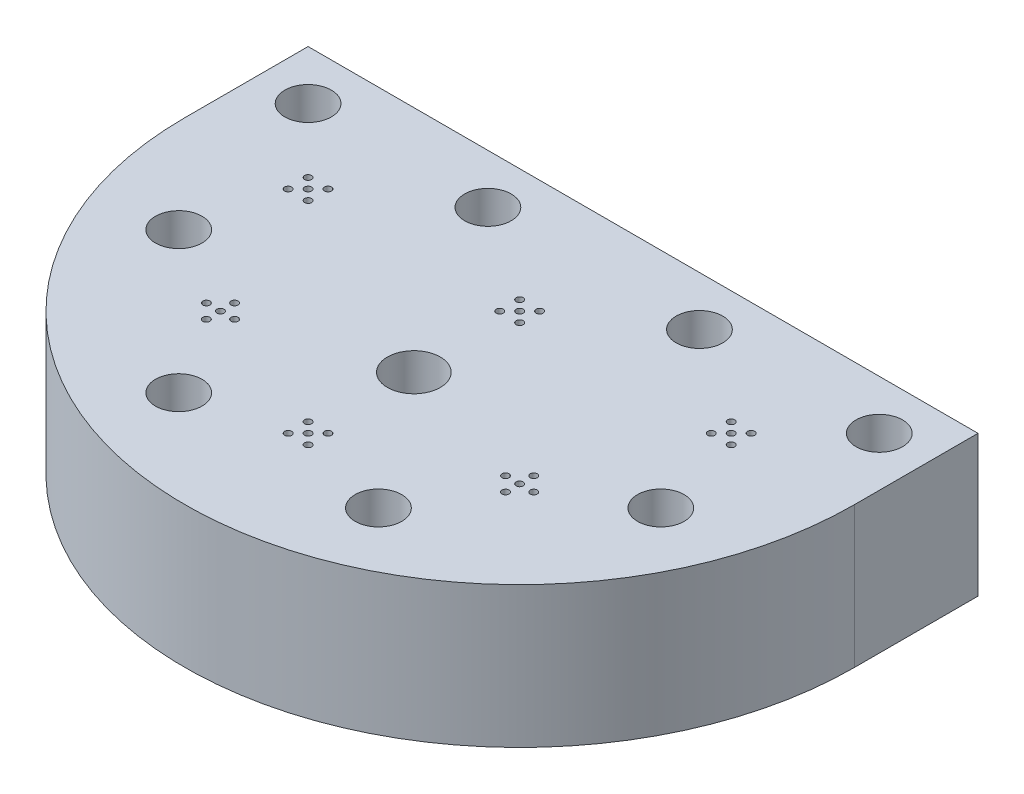
SolidWorks part; units mm, degrees
ref_plane "Front Plane" through (0, 0, 0) normal (0, 0, 1) x (1, 0, 0)
ref_plane "Top Plane" through (0, 0, 0) normal (0, 1, 0) x (1, 0, 0)
ref_plane "Right Plane" through (0, 0, 0) normal (1, 0, 0) x (0, 0, -1)
sketch "Sketch1" plane through (0, 0, 0) normal (0, 1, 0) x (1, 0, 0)
  line L0 (-47.5, 0) -> (47.5, 0)
  line L1 (-47.5, 0) -> (-47.5, -17.5)
  line L2 (47.5, 0) -> (47.5, -17.5)
  arc A0 (-47.5, -17.5) -> (47.5, -17.5) centre (0, -17.5) ccw
  point P4 (0, 0)
  dimension "D1" = 95
  dimension "D2" = 17.5
extrude "Boss-Extrude1" add sketch "Sketch1" along normal blind 20
sketch "Sketch2" plane through (0, 0, 0) normal (0, -1, 0) x (1, 0, 0)
  line L0 (30, 17.5) -> (-30, 17.5) construction
  line L1 (47.5, 0) -> (-47.5, 0) construction
  line L2 (0, 17.5) -> (21.2132, 38.7132) construction
  line L3 (0, 17.5) -> (-21.2132, 38.7132) construction
  arc A0 (30, 17.5) -> (-30, 17.5) centre (0, 17.5) ccw construction
  circle A1 centre (30, 17.5) radius 7.5
  circle A2 centre (0, 17.5) radius 7.5
  circle A3 centre (-30, 17.5) radius 7.5
  circle A4 centre (0, 47.5) radius 7.5
  circle A5 centre (-21.2132, 38.7132) radius 7.5
  circle A6 centre (21.2132, 38.7132) radius 7.5
  dimension "D1" = 60
  dimension "D3" = 15
  dimension "D2" = 17.5
  dimension "D4" = 45
  dimension "D5" = 45
extrude "Cut-Extrude1" cut sketch "Sketch2" against normal blind 9.5
ref_plane "Plane1" through (0, 0, 17.5) normal (0, 0, -1) x (-1, 0, 0)
sketch "Sketch3" plane through (0, 0, 17.5) normal (0, 0, -1) x (-1, 0, 0)
  line L0 (0, 9.5) -> (0, 17)
  line L1 (0, 9.5) -> (7.5, 9.5)
  line L2 (-7.5, 9.5) -> (7.5, 9.5) construction
  arc A0 (0, 17) -> (7.5, 9.5) centre (0, 9.5) cw
  point P4 (17.951, 11.8486)
  point P6 (0, 0)
  point P8 (0, 0)
  dimension "D1" = 7.5
revolve "Cut-Revolve1" cut sketch "Sketch3" angle 360 about L0
sketch "Sketch4" plane through (0, 0, 17.5) normal (0, 0, -1) x (-1, 0, 0)
  line L0 (-30, 9.5) -> (-30, 17)
  line L1 (-30, 9.5) -> (-22.5, 9.5)
  line L2 (-37.5, 9.5) -> (-22.5, 9.5) construction
  line L3 (-37.5, 9.5) -> (-22.5, 9.5) construction
  arc A0 (-30, 17) -> (-22.5, 9.5) centre (-30, 9.5) cw
  point P4 (0, 0)
  point P6 (0, 0)
  point P7 (-30.2611, 9.5)
  point P8 (-30, 9.5)
  point P9 (0, 0)
revolve "Cut-Revolve2" cut sketch "Sketch4" angle 360 about L0
ref_axis "Axis1" through (0, 9.5, 17.5) along (0, -1, 0)
pattern_circular "CirPattern1" count 5 every 45 about axis through (0, 9.5, 17.5) along (0, -1, 0) of "Cut-Revolve2"
sketch "Sketch5" plane through (0, 20, 0) normal (0, 1, 0) x (1, 0, 0)
  line L1 (1.4142, -18.9142) -> (-1.4142, -18.9142) construction
  line L2 (1.4142, -18.9142) -> (1.4142, -16.0858) construction
  line L3 (1.4142, -16.0858) -> (-1.4142, -16.0858) construction
  line L4 (-1.4142, -18.9142) -> (-1.4142, -16.0858) construction
  line L5 (1.4142, -18.9142) -> (-1.4142, -16.0858) construction
  line L6 (1.4142, -16.0858) -> (-1.4142, -18.9142) construction
  circle A0 centre (30, -17.5) radius 7.5 construction
  circle A1 centre (21.2132, -38.7132) radius 7.5 construction
  circle A2 centre (0, -17.5) radius 7.5 construction
  circle A3 centre (-30, -17.5) radius 7.5 construction
  circle A4 centre (-21.2132, -38.7132) radius 7.5 construction
  circle A5 centre (0, -47.5) radius 7.5 construction
  circle A6 centre (30, -17.5) radius 7.5 construction
  circle A7 centre (21.2132, -38.7132) radius 7.5 construction
  circle A8 centre (0, -17.5) radius 7.5 construction
  circle A9 centre (-30, -17.5) radius 7.5 construction
  circle A10 centre (-21.2132, -38.7132) radius 7.5 construction
  circle A11 centre (0, -47.5) radius 7.5 construction
  circle A12 centre (21.2132, -38.7132) radius 0.5
  circle A13 centre (21.2132, -38.7132) radius 2 construction
  circle A14 centre (21.2132, -40.7132) radius 0.5
  circle A15 centre (19.2132, -38.7132) radius 0.5
  circle A16 centre (23.2132, -38.7132) radius 0.5
  circle A17 centre (21.2132, -36.7132) radius 0.5
  circle A18 centre (1.4142, -46.0858) radius 0.5
  circle A19 centre (0, -47.5) radius 2 construction
  circle A20 centre (1.4142, -48.9142) radius 0.5
  circle A21 centre (0, -47.5) radius 0.5
  circle A22 centre (-1.4142, -46.0858) radius 0.5
  circle A23 centre (-1.4142, -48.9142) radius 0.5
  circle A24 centre (-19.2132, -38.7132) radius 0.5
  circle A25 centre (-21.2132, -38.7132) radius 2 construction
  circle A26 centre (-21.2132, -40.7132) radius 0.5
  circle A27 centre (-21.2132, -38.7132) radius 0.5
  circle A28 centre (-21.2132, -36.7132) radius 0.5
  circle A29 centre (-23.2132, -38.7132) radius 0.5
  circle A30 centre (-28.5858, -18.9142) radius 0.5
  circle A31 centre (-30, -17.5) radius 2 construction
  circle A32 centre (-31.4142, -18.9142) radius 0.5
  circle A33 centre (-30, -17.5) radius 0.5
  circle A34 centre (-28.5858, -16.0858) radius 0.5
  circle A35 centre (-31.4142, -16.0858) radius 0.5
  circle A36 centre (-21.2132, 1.7132) radius 0.5 [skipped]
  circle A37 centre (-21.2132, 3.7132) radius 2 construction
  circle A38 centre (-23.2132, 3.7132) radius 0.5 [skipped]
  circle A39 centre (-21.2132, 3.7132) radius 0.5 [skipped]
  circle A40 centre (-19.2132, 3.7132) radius 0.5 [skipped]
  circle A41 centre (-21.2132, 5.7132) radius 0.5 [skipped]
  circle A42 centre (-1.4142, 11.0858) radius 0.5 [skipped]
  circle A43 centre (0, 12.5) radius 2 construction
  circle A44 centre (-1.4142, 13.9142) radius 0.5 [skipped]
  circle A45 centre (0, 12.5) radius 0.5 [skipped]
  circle A46 centre (1.4142, 11.0858) radius 0.5 [skipped]
  circle A47 centre (1.4142, 13.9142) radius 0.5 [skipped]
  circle A48 centre (19.2132, 3.7132) radius 0.5 [skipped]
  circle A49 centre (21.2132, 3.7132) radius 2 construction
  circle A50 centre (21.2132, 5.7132) radius 0.5 [skipped]
  circle A51 centre (21.2132, 3.7132) radius 0.5 [skipped]
  circle A52 centre (21.2132, 1.7132) radius 0.5 [skipped]
  circle A53 centre (23.2132, 3.7132) radius 0.5 [skipped]
  circle A54 centre (28.5858, -16.0858) radius 0.5
  circle A55 centre (30, -17.5) radius 2 construction
  circle A56 centre (31.4142, -16.0858) radius 0.5
  circle A57 centre (30, -17.5) radius 0.5
  circle A58 centre (28.5858, -18.9142) radius 0.5
  circle A59 centre (31.4142, -18.9142) radius 0.5
  circle A60 centre (0, -17.5) radius 2 construction
  circle A61 centre (1.4142, -18.9142) radius 0.5
  circle A62 centre (-1.4142, -18.9142) radius 0.5
  circle A63 centre (0, -17.5) radius 0.5
  circle A64 centre (1.4142, -16.0858) radius 0.5
  circle A65 centre (-1.4142, -16.0858) radius 0.5
  point P4 (1.4142, -16.2052)
  point P108 (1.5735, -18.7345)
  point P111 (-1.5715, -18.7371)
  dimension "D1" = 1
  dimension "D2" = 4
  dimension "D3" = 8
  dimension "D4" = 1
extrude "Cut-Extrude2" cut sketch "Sketch5" against normal through all
hole_wizard "M6 Clearance Hole1" positions "Sketch6" profile "Sketch7" hole size "M6" standard "ANSI Metric" end condition through all
sketch "Sketch6" plane through (0, 20, 0) normal (0, 1, 0) x (1, 0, 0)
  line L0 (-40.5, -7) -> (40.5, -7) construction
  line L2 (47.5, -17.5) -> (47.5, 0) construction
  line L3 (47.5, 0) -> (-47.5, 0) construction
  line L4 (-47.5, 0) -> (-47.5, -17.5) construction
  line L5 (11, -17.5) -> (-11, -17.5) construction
  line L6 (0, -17.5) -> (-34.1835, -31.6593) construction
  line L8 (0, -17.5) -> (-14.1593, -51.6835) construction
  line L10 (0, -17.5) -> (14.1593, -51.6835) construction
  line L12 (0, -17.5) -> (34.1835, -31.6593) construction
  line L14 (30, -17.5) -> (-30, -17.5) construction
  arc A0 (-37, -17.5) -> (37, -17.5) centre (0, -17.5) ccw
  point P0 (-40.5, -7)
  point P2 (-15, -7)
  point P4 (15, -7)
  point P6 (40.5, -7)
  point P8 (-34.1835, -31.6593)
  point P10 (-14.1593, -51.6835)
  point P12 (14.1593, -51.6835)
  point P14 (34.1835, -31.6593)
  dimension "D6" = 37
  dimension "D1" = 7
  dimension "D2" = 7
  dimension "D3" = 7
  dimension "D4" = 15
  dimension "D5" = 15
  dimension "D7" = 22.5
  dimension "D8" = 22.5
  dimension "D9" = 45
  dimension "D10" = 45
sketch "Sketch7" plane through (-40.5, 20, 7) normal (1, 0, 0) x (0, 0, 1)
  line L0 (0, 0) -> (0, 20)
  line L1 (0, 20) -> (3.3, 20)
  line L2 (3.3, 20) -> (3.3, 0)
  line L5 (3.3, 0) -> (0, 0)
  line L11 (0, -6.35) -> (0, 107.95) construction
  dimension "Thru Hole Dia." = 6.6
  dimension "Thru Hole Depth" = 20
sketch "Sketch8" plane through (0, 20, 0) normal (0, 1, 0) x (1, 0, 0)
  line L0 (0, -17.5) -> (0, -47.5) construction
  circle A0 centre (0, -32.5) radius 3.75
  point P6 (0, 0)
  dimension "D1" = 7.5
extrude "Cut-Extrude3" cut sketch "Sketch8" against normal through all
sketch "Sketch9" plane through (0, 0, 0) normal (1, 0, 0) x (0, 0, -1)
  line L0 (-5, 0) -> (-5, 2.5) construction
  line L1 (-5, 0) -> (-7.5, 0) construction
  line L2 (-17.5, 0) -> (0, 0) construction
  line L3 (-5, 2.627) -> (-5, 0)
  line L4 (-5, 0) -> (-7.627, 0)
  arc A0 (-5, 2.5) -> (-7.5, 0) centre (-5, 0) ccw construction
  arc A1 (-5, 2.627) -> (-7.627, 0) centre (-5, 0) ccw
  dimension "D1" = 5
  dimension "D2" = 2.5
  dimension "D3" = 0.127
revolve "Cut-Revolve3" cut sketch "Sketch9" angle 360 about L3
sketch "Sketch10" plane through (0, 0, 0) normal (1, 0, 0) x (0, 0, -1)
  line L0 (-60.5, 0) -> (-60.5, 2.5) construction
  line L1 (-60.5, 0) -> (-63, 0) construction
  line L3 (-7.627, 0) -> (-2.373, 0) construction
  line L4 (-63.127, 0) -> (-60.5, 0)
  line L5 (-60.5, 0) -> (-60.5, 2.627)
  arc A0 (-60.5, 2.5) -> (-63, 0) centre (-60.5, 0) ccw construction
  arc A1 (-60.5, 2.627) -> (-63.127, 0) centre (-60.5, 0) ccw
  dimension "D1" = 60.5
  dimension "D2" = 2.5
  dimension "D3" = 0.127
revolve "Cut-Revolve4" cut sketch "Sketch10" angle 360 about L5
